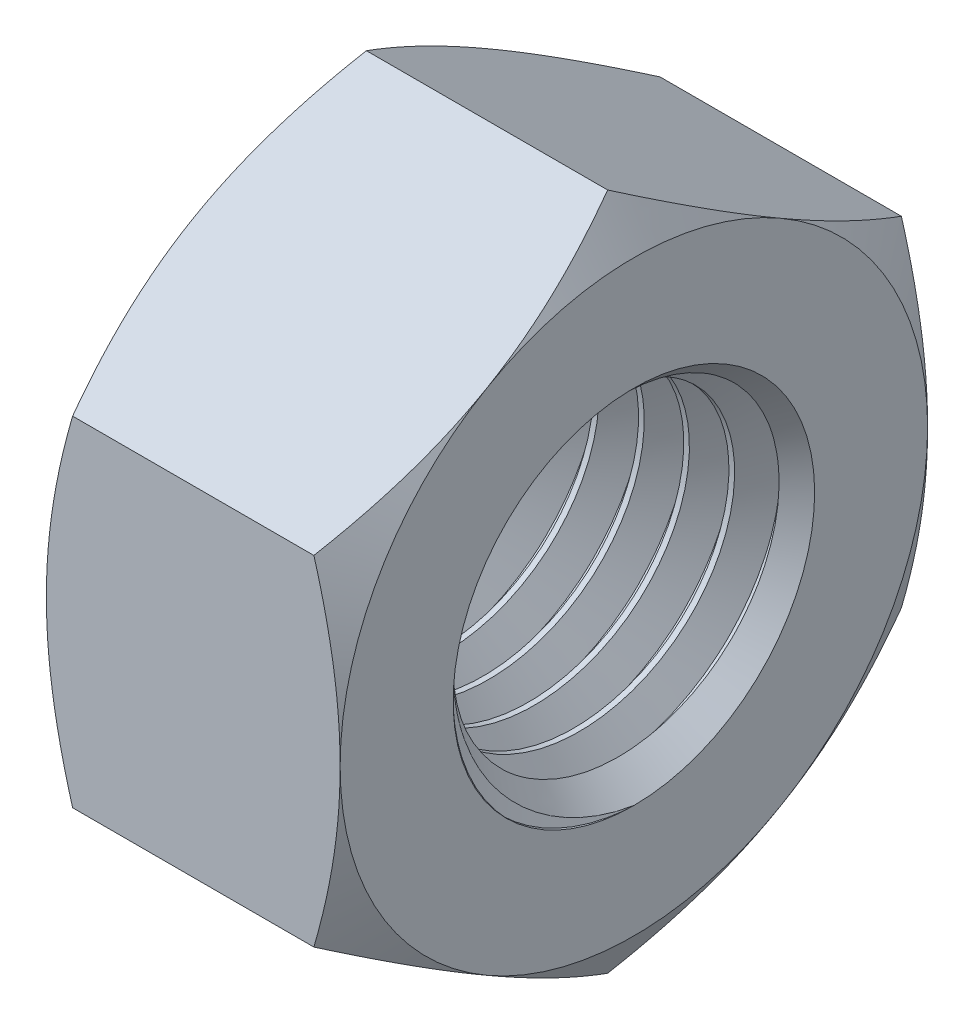
SolidWorks part; units mm, degrees
ref_plane "Front Plane" through (0, 0, 0) normal (0, 0, 1) x (1, 0, 0)
ref_plane "Top Plane" through (0, 0, 0) normal (0, 1, 0) x (1, 0, 0)
ref_plane "Right Plane" through (0, 0, 0) normal (1, 0, 0) x (0, 0, -1)
sketch "Sketch1" plane through (0, 0, 0) normal (1, 0, 0) x (0, 0, -1)
  line L7 (-6.5, -3.7528) -> (0, -7.5056)
  line L8 (0, -7.5056) -> (6.5, -3.7528)
  line L9 (6.5, -3.7528) -> (6.5, 3.7528)
  line L10 (6.5, 3.7528) -> (0, 7.5056)
  line L11 (0, 7.5056) -> (-6.5, 3.7528)
  line L12 (-6.5, 3.7528) -> (-6.5, -3.7528)
  circle A0 centre (0, 0) radius 6.5 construction
  dimension "Width" = 13
extrude "Boss-Extrude1" add sketch "Sketch1" along normal mid plane 6.5
sketch "Sketch2" plane through (-3.25, 0, 0) normal (1, 0, 0) x (0, 0, -1)
  circle A0 centre (0, 0) radius 4
  dimension "Thread Size" = 8
extrude "Cut-Extrude1" cut sketch "Sketch2" along normal blind 6.5 and the other way through all
sketch "Sketch11" plane through (-3.25, 0, 0) normal (-1, 0, 0) x (0, 0, 1)
  line L0 (6.5, 3.7528) -> (6.5, -3.7528) construction
  circle A0 centre (0, 0) radius 6.5
extrude "Cut-Extrude7" cut sketch "Sketch11" against normal through all draft 60 flip side to cut
mirror "Mirror4" about plane through (0, 0, 0) normal (1, 0, 0) of "Cut-Extrude7"
sketch "Sketch3" plane through (-3.25, 0, 0) normal (-1, 0, 0) x (0, 0, 1)
  circle A0 centre (0, 0) radius 4 construction
  circle A1 centre (0, 0) radius 4
curve "Helix/Spiral1" pitch 1 height 7.5 radius 4 centre (-3.25, 0, 0) axis (1, 0, 0) start towards (0, 1, 0) parameters "Pitch"=1
sketch "Sketch4" plane through (0, 0, 0) normal (0, 0, 1) x (1, 0, 0)
  line L0 (-4.1875, 4.1083) -> (-3.1875, 4.1083) construction
  line L1 (-3.1875, 4.1083) -> (-3.6875, 3.2422) construction
  line L2 (-3.6875, 3.2422) -> (-4.1875, 4.1083) construction
  line L3 (-3.6875, 3.2422) -> (-3.6875, 3.3505) construction
  line L4 (-3.6875, 4.1083) -> (-3.6875, 4) construction
  line L5 (-4.1562, 4.0541) -> (-3.2187, 4.0541) construction
  line L6 (-3.25, 4) -> (-4.125, 4) construction
  line L7 (-3.75, 3.3505) -> (-3.625, 3.3505) construction
  point P10 (-3.6875, 4.0541)
  dimension "Pitch" = 1
  dimension "D2" = 0.125
sketch "Sketch6" plane through (0, 0, 0) normal (0, 0, 1) x (1, 0, 0)
  line L0 (-3.1875, 4.1083) -> (-3.6875, 3.2422) construction
  line L1 (-3.75, 3.3505) -> (-3.625, 3.3505) construction
  line L2 (-3.6875, 3.2422) -> (-4.1875, 4.1083) construction
  line L3 (-4.1562, 4.0541) -> (-3.2187, 4.0541) construction
  line L4 (-3.2187, 4.0541) -> (-3.625, 3.3505)
  line L5 (-3.75, 3.3505) -> (-3.625, 3.3505)
  line L6 (-3.75, 3.3505) -> (-4.1562, 4.0541)
  line L7 (-4.1562, 4.0541) -> (-3.2187, 4.0541)
sweep "Sweep1" add profiles "Sketch6" path "Helix/Spiral1"
sketch "Sketch7" plane through (-3.25, 0, 0) normal (-1, 0, 0) x (0, 0, 1)
  arc A6 (-3.25, 5.6292) -> (-6.5, 0) centre (0, 0) ccw
  arc A7 (-3.25, 5.6292) -> (-6.5, 0) centre (0, 0) ccw
  arc A8 (-6.5, 0) -> (-3.25, -5.6292) centre (0, 0) ccw
  arc A9 (-6.5, 0) -> (-3.25, -5.6292) centre (0, 0) ccw
  arc A10 (-3.25, -5.6292) -> (3.25, -5.6292) centre (0, 0) ccw
  arc A11 (-3.25, -5.6292) -> (3.25, -5.6292) centre (0, 0) ccw
  arc A12 (3.25, -5.6292) -> (6.5, 0) centre (0, 0) ccw
  arc A13 (3.25, -5.6292) -> (6.5, 0) centre (0, 0) ccw
  arc A14 (6.5, 0) -> (3.25, 5.6292) centre (0, 0) ccw
  arc A15 (6.5, 0) -> (3.25, 5.6292) centre (0, 0) ccw
  arc A16 (3.25, 5.6292) -> (-3.25, 5.6292) centre (0, 0) ccw
  arc A17 (3.25, 5.6292) -> (-3.25, 5.6292) centre (0, 0) ccw
  dimension "D1" = 0
extrude "Cut-Extrude2" cut sketch "Sketch7" along normal through all
sketch "Sketch10" plane through (-3.25, 0, 0) normal (-1, 0, 0) x (0, 0, 1)
  circle A0 centre (0, 0) radius 4 construction
  circle A1 centre (0, 0) radius 4
extrude "Cut-Extrude6" cut sketch "Sketch10" against normal through all draft 45
mirror "Mirror1" about plane through (0, 0, 0) normal (1, 0, 0) of "Cut-Extrude6", "Cut-Extrude2"
ref_plane "Contact Plane 1" through (-3.25, 0, 0) normal (-1, 0, 0) x (0, 0, 1)
ref_plane "Contact Plane 2" through (3.25, 0, 0) normal (1, 0, 0) x (0, 0, -1)
ref_axis "Contact Axis 1" through (-3.9894, 0, 0) along (1, 0, 0)
equation "\"D1@Cut-Extrude1\" = \"Height@Boss-Extrude1\""
equation "\"D3@Helix/Spiral1\" = \"D1@Cut-Extrude1\" + \"Pitch@Helix/Spiral1\""
equation "\"D2@Sketch4\" = \"Pitch@Sketch4\" / 8"
equation "\"Pitch@Sketch4\" = \"Pitch@Helix/Spiral1\""
